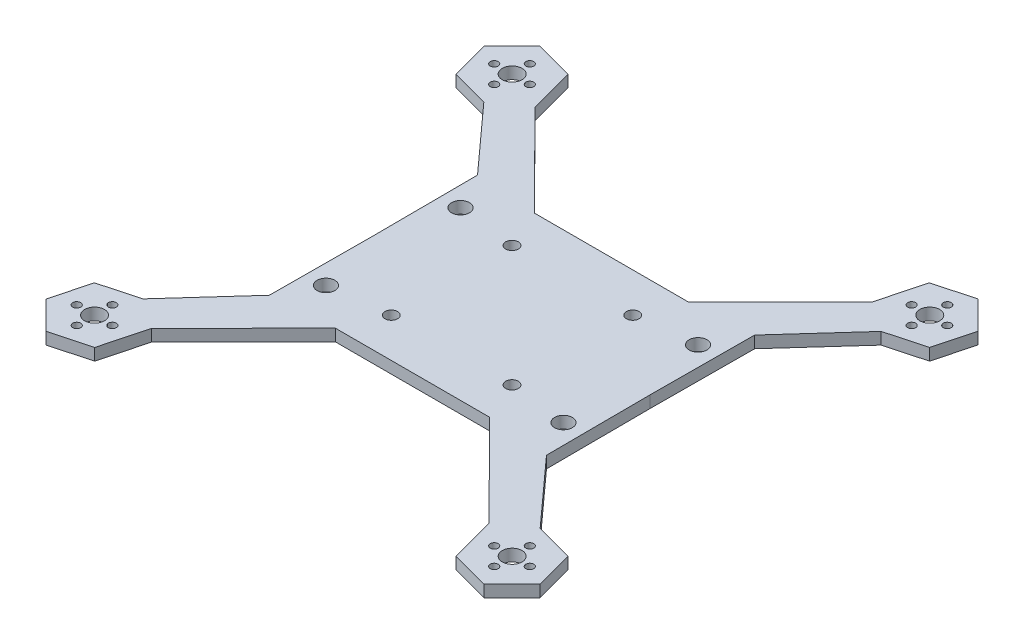
SolidWorks part; units mm, degrees
material "T700G"
ref_plane "Front Plane" through (0, 0, 0) normal (0, 0, 1) x (1, 0, 0)
ref_plane "Top Plane" through (0, 0, 0) normal (0, 1, 0) x (1, 0, 0)
ref_plane "Right Plane" through (0, 0, 0) normal (1, 0, 0) x (0, 0, -1)
sketch "Sketch1" plane through (0, 0, 0) normal (0, 1, 0) x (1, 0, 0)
  line L5 (-35, -35) -> (42.6186, 42.6186) construction
  line L6 (-35, 35) -> (35, -35) construction
  line L9 (0, 0) -> (42.4264, 42.4264) construction
  line L10 (52.7307, 48.2307) -> (52.7307, 57.2307) construction
  line L11 (30, 17) -> (30, 0) construction
  line L12 (0, 0) -> (0, 23.6863) construction
  line L28 (0, 0) -> (-174.2372, 0) construction
  line L41 (31.9599, 25.1581) -> (-25.1581, 25.1581) construction
  line L70 (42.6186, 48.4021) -> (19.4638, 25.1581)
  line L72 (48.2307, 52.7307) -> (57.2307, 52.7307) construction
  line L74 (48.2307, 52.7307) -> (52.7307, 48.2307) construction
  line L75 (55.3003, 62.3949) -> (45.646, 59.7881)
  line L77 (45.646, 59.7881) -> (42.6186, 48.4021)
  line L80 (50.185, 43.0729) -> (59.8153, 45.6732)
  line L83 (59.8153, 45.6732) -> (62.3849, 55.3374)
  line L85 (62.3849, 55.3374) -> (55.3003, 62.3949)
  line L87 (50.185, 43.0729) -> (35, 26.2883)
  line L88 (35, 26.2883) -> (34.873, 0)
  line L89 (34.873, -11.873) -> (34.873, 11.873) construction
  line L90 (-21.8355, 25.1581) -> (21.8355, 25.1581)
  line L94 (35, -26.2883) -> (34.873, 0)
  line L100 (48.2307, -52.7307) -> (52.7307, -48.2307) construction
  line L101 (48.2307, -52.7307) -> (57.2307, -52.7307) construction
  line L102 (52.7307, -48.2307) -> (52.7307, -57.2307) construction
  line L106 (62.3849, -55.3374) -> (55.3003, -62.3949)
  line L111 (59.8153, -45.6732) -> (62.3849, -55.3374)
  line L115 (50.185, -43.0729) -> (59.8153, -45.6732)
  line L116 (45.646, -59.7881) -> (42.6186, -48.4021)
  line L119 (55.3003, -62.3949) -> (45.646, -59.7881)
  line L127 (50.185, -43.0729) -> (35, -26.2883)
  line L128 (35, 26.2883) -> (34.873, 0)
  line L129 (35, -26.2883) -> (34.873, 0)
  line L135 (42.6186, -48.4021) -> (19.4638, -25.1581)
  line L138 (40.4517, 52.7386) -> (49.1512, 44.0725) [skipped]
  line L139 (-21.8355, -25.1581) -> (21.8355, -25.1581)
  line L140 (-48.2307, 52.7307) -> (-52.7307, 48.2307) construction
  line L141 (-48.2307, 52.7307) -> (-57.2307, 52.7307) construction
  line L142 (-52.7307, 48.2307) -> (-52.7307, 57.2307) construction
  line L143 (-62.3849, 55.3374) -> (-55.3003, 62.3949)
  line L144 (-59.8153, 45.6732) -> (-62.3849, 55.3374)
  line L145 (-50.185, 43.0729) -> (-59.8153, 45.6732)
  line L146 (-45.646, 59.7881) -> (-42.6186, 48.4021)
  line L147 (-55.3003, 62.3949) -> (-45.646, 59.7881)
  line L148 (-50.185, 43.0729) -> (-35, 26.2883)
  line L149 (-42.6186, 48.4021) -> (-19.4638, 25.1581)
  line L150 (-35, 26.2883) -> (-34.873, 0)
  line L151 (-35, -26.2883) -> (-34.873, 0)
  line L152 (-50.185, -43.0729) -> (-35, -26.2883)
  line L153 (-42.6186, -48.4021) -> (-19.4638, -25.1581)
  line L154 (-52.7307, -48.2307) -> (-52.7307, -57.2307) construction
  line L155 (-48.2307, -52.7307) -> (-57.2307, -52.7307) construction
  line L156 (-48.2307, -52.7307) -> (-52.7307, -48.2307) construction
  line L157 (-55.3003, -62.3949) -> (-45.646, -59.7881)
  line L158 (-45.646, -59.7881) -> (-42.6186, -48.4021)
  line L159 (-50.185, -43.0729) -> (-59.8153, -45.6732)
  line L160 (-59.8153, -45.6732) -> (-62.3849, -55.3374)
  line L161 (-62.3849, -55.3374) -> (-55.3003, -62.3949)
  circle A0 centre (-15.25, 15.25) radius 1.6
  circle A1 centre (15.25, 15.25) radius 1.6
  circle A2 centre (15.25, -15.25) radius 1.6
  circle A3 centre (-15.25, -15.25) radius 1.6
  circle A18 centre (30, 17) radius 2.25
  circle A19 centre (30, -17) radius 2.25
  circle A20 centre (-30, -17) radius 2.25
  circle A21 centre (-30, 17) radius 2.25
  circle A69 centre (52.7307, 52.7307) radius 8.6603 construction
  circle A70 centre (52.7307, 57.2307) radius 1
  circle A71 centre (52.7307, 48.2307) radius 1
  circle A72 centre (48.2307, 52.7307) radius 1
  circle A73 centre (57.2307, 52.7307) radius 1
  circle A124 centre (52.7307, -52.7307) radius 8.6603 construction
  circle A125 centre (57.2307, -52.7307) radius 1
  circle A126 centre (48.2307, -52.7307) radius 1
  circle A127 centre (52.7307, -48.2307) radius 1
  circle A128 centre (52.7307, -57.2307) radius 1
  circle A129 centre (-52.7307, 52.7307) radius 8.6603 construction
  circle A130 centre (-57.2307, 52.7307) radius 1
  circle A131 centre (-48.2307, 52.7307) radius 1
  circle A132 centre (-52.7307, 48.2307) radius 1
  circle A133 centre (-52.7307, 57.2307) radius 1
  circle A134 centre (-52.7307, -52.7307) radius 8.6603 construction
  circle A135 centre (-52.7307, -57.2307) radius 1
  circle A136 centre (-52.7307, -48.2307) radius 1
  circle A137 centre (-48.2307, -52.7307) radius 1
  circle A138 centre (-57.2307, -52.7307) radius 1
  point P0 (0, 0)
  point P8 (52.7307, 52.7307)
  point P9 (52.7307, 52.7307)
  point P17 (0, 0)
  point P45 (24.8566, 0)
  point P47 (30, 0)
  point P90 (0, 25.1581)
  point P95 (0, -25.1581)
  point P96 (0, 25.1581)
  point P99 (0, 25.1581)
  point P110 (0, -25.1581)
  point P118 (0, 0)
  point P126 (0, -25.1581)
  dimension "D3" = 3.2
  dimension "D16" = 4.5
  dimension "D1" = 70
  dimension "D2" = 4.5
  dimension "D4" = 30.5
  dimension "D6" = 4.5
  dimension "D7" = 20
  dimension "D15" = 17
  dimension "D12" = 30
  dimension "D5" = 4
  dimension "D17" = 2
extrude "Boss-Extrude1" add sketch "Sketch1" along normal blind 3 contours L144 A21 A0 A1 A2 A3 region at (0, 0, 0)
sketch "Sketch7" plane through (0, 3, 0) normal (0, 1, 0) x (1, 0, 0)
  line L0 (-57.2307, -52.7307) -> (-48.2307, -52.7307) construction
  line L1 (-52.7307, -57.2307) -> (-52.7307, -48.2307) construction
  line L2 (0, 0) -> (-75.1546, 0) construction
  line L3 (0, 0) -> (0, 55.538) construction
  circle A0 centre (-52.7307, -52.7307) radius 0.75
  circle A1 centre (-52.7307, 52.7307) radius 0.75
  circle A2 centre (52.7307, 52.7307) radius 0.75
  circle A3 centre (52.7307, -52.7307) radius 0.75
  dimension "D1" = 1.5
extrude "Boss-Extrude4" add sketch "Sketch7" along normal blind 0.05
sketch "Sketch8" plane through (0, 3, 0) normal (0, 1, 0) x (1, 0, 0)
  circle A0 centre (-52.7307, -52.7307) radius 2.5
  circle A1 centre (52.7693, -52.7307) radius 2.5
  circle A2 centre (52.7693, 52.7693) radius 2.5
  circle A3 centre (-52.7307, 52.7693) radius 2.5
  dimension "D1" = 2
  dimension "D2" = 2
extrude "Cut-Extrude7" cut sketch "Sketch8" against normal blind 10
